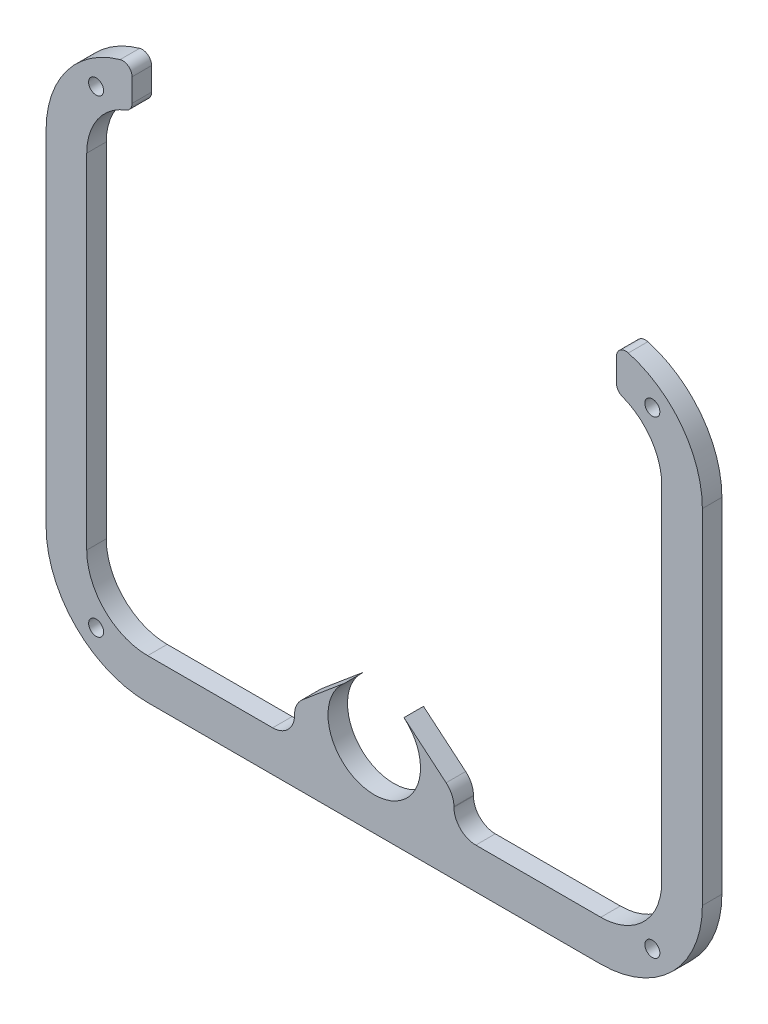
SolidWorks part; units mm, degrees
material "Delrin 2700 NC010, Low Viscosity Acetal Copolymer (SS)"
ref_plane "Front Plane" through (0, 0, 0) normal (0, 0, 1) x (1, 0, 0)
ref_plane "Top Plane" through (0, 0, 0) normal (0, 1, 0) x (1, 0, 0)
ref_plane "Right Plane" through (0, 0, 0) normal (1, 0, 0) x (0, 0, -1)
sketch "Sketch1" plane through (0, 0, 0) normal (0, 0, 1) x (1, 0, 0)
  line L0 (-18.415, -18.923) -> (-9.6321, -18.923)
  line L1 (18.415, 22.225) -> (-18.415, 22.225)
  line L2 (26.67, 13.97) -> (26.67, -13.97)
  line L3 (18.415, -22.225) -> (-18.415, -22.225)
  line L4 (-26.67, 13.97) -> (-26.67, -13.97)
  line L5 (26.67, 22.225) -> (-26.67, -22.225) construction
  line L6 (26.67, -22.225) -> (-26.67, 22.225) construction
  line L7 (9.6321, -18.923) -> (18.415, -18.923)
  line L10 (-23.368, 13.97) -> (-23.368, -13.97)
  line L11 (-1000, 0) -> (49000, 0) construction
  line L12 (-23.368, 0) -> (-23.368, -1.27)
  line L13 (23.368, 13.97) -> (23.368, -13.97)
  line L14 (18.415, 18.923) -> (-18.415, 18.923)
  line L18 (0, 18.923) -> (0, -18.415) construction
  line L21 (2.4164, -12.8683) -> (9.6321, -18.923)
  line L22 (-2.4164, -12.8683) -> (-9.6321, -18.923)
  line L36 (18.415, -18.923) -> (-18.415, -18.923) construction
  arc A0 (-2.4164, -12.8683) -> (2.4164, -12.8683) centre (0, -15.748) ccw
  arc A1 (-18.415, 22.225) -> (-26.67, 13.97) centre (-18.415, 13.97) ccw
  arc A2 (18.415, 22.225) -> (26.67, 13.97) centre (18.415, 13.97) cw
  arc A3 (26.67, -13.97) -> (18.415, -22.225) centre (18.415, -13.97) cw
  arc A4 (-18.415, -22.225) -> (-26.67, -13.97) centre (-18.415, -13.97) cw
  arc A7 (18.415, 18.923) -> (23.368, 13.97) centre (18.415, 13.97) cw
  arc A8 (-18.415, 18.923) -> (-23.368, 13.97) centre (-18.415, 13.97) ccw
  circle A9 centre (-22.606, 19.05) radius 0.6096
  circle A10 centre (22.606, 19.05) radius 0.6096
  circle A11 centre (-22.606, -19.05) radius 0.6096
  circle A12 centre (22.606, -19.05) radius 0.6096
  arc A13 (-18.415, -18.923) -> (-23.368, -13.97) centre (-18.415, -13.97) cw construction
  arc A14 (23.368, -13.97) -> (18.415, -18.923) centre (18.415, -13.97) cw construction
  arc A15 (-23.368, -13.97) -> (-18.415, -18.923) centre (-18.415, -13.97) ccw
  arc A16 (18.415, -18.923) -> (23.368, -13.97) centre (18.415, -13.97) ccw
  point P0 (0, 0)
  dimension "D4" = 7.5184
  dimension "D6" = 8.255
  dimension "D7" = 8.255
  dimension "D8" = 8.255
  dimension "D9" = 8.255
  dimension "D5" = 1.2192
  dimension "D1" = 53.34
  dimension "D2" = 44.45
  dimension "D10" = 3.302
  dimension "D3" = 3.175
  dimension "D11" = 3.175
  dimension "D12" = 4.064
  dimension "D13" = 15.748
extrude "Boss-Extrude1" add sketch "Sketch1" along normal blind 1.5875 contours A4 L3 A3 L2 A2 L1 A1 L4 A16 L7 L21 A0 L22 L0 A15 L10 A8 L14 A7 L13 A12 A10 A9 A11 region at (23.7612, 19.3162, 0)
sketch "Sketch2" plane through (0, 0, 1.5875) normal (0, 0, 1) x (1, 0, 0)
  line L1 (-9.6321, -18.923) -> (-6.477, -18.923)
  line L2 (-9.6321, -18.923) -> (-9.6321, -16.2756)
  line L3 (-9.6321, -16.2756) -> (-6.477, -16.2756)
  line L4 (-6.477, -18.923) -> (-6.477, -16.2756)
  line L5 (0, -1000) -> (0, 49000) construction
  line L6 (9.6321, -18.923) -> (9.6321, -16.2756)
  line L7 (9.6321, -16.2756) -> (6.477, -16.2756)
  line L8 (6.477, -18.923) -> (6.477, -16.2756)
  line L9 (9.6321, -18.923) -> (6.477, -18.923)
  line L11 (-18.415, 18.923) -> (18.415, 18.923)
  line L12 (-19.685, 18.7574) -> (-19.685, 22.225)
  line L13 (-19.685, 22.225) -> (19.685, 22.225)
  line L14 (19.685, 18.7574) -> (19.685, 22.225)
  line L16 (18.415, 18.923) -> (-18.415, 18.923) construction
  line L17 (-2.4164, -12.8683) -> (-9.6321, -18.923) construction
  line L18 (18.415, 22.225) -> (-18.415, 22.225) construction
  arc A0 (23.368, 13.97) -> (18.415, 18.923) centre (18.415, 13.97) ccw construction
  arc A1 (-18.415, 18.923) -> (-23.368, 13.97) centre (-18.415, 13.97) ccw construction
  arc A2 (19.685, 18.7574) -> (18.415, 18.923) centre (18.415, 13.97) ccw
  arc A3 (-18.415, 18.923) -> (-19.685, 18.7574) centre (-18.415, 13.97) ccw
  point P25 (0, 22.225)
  dimension "D1" = 6.477
  dimension "D2" = 39.37
extrude "Cut-Extrude1" cut sketch "Sketch2" against normal up to next
fillet "Fillet1" radius 1.778 4 edges at (6.477, -18.923, 0.7937) (6.477, -16.2756, 0.7937) (-6.477, -18.923, 0.7937) (-6.477, -16.2756, 0.7937)
fillet "Fillet2" radius 0.762 4 edges at (19.685, 22.1267, 0.7937) (19.685, 18.7574, 0.7937) (-19.685, 18.7574, 0.7937) (-19.685, 22.1267, 0.7937)
